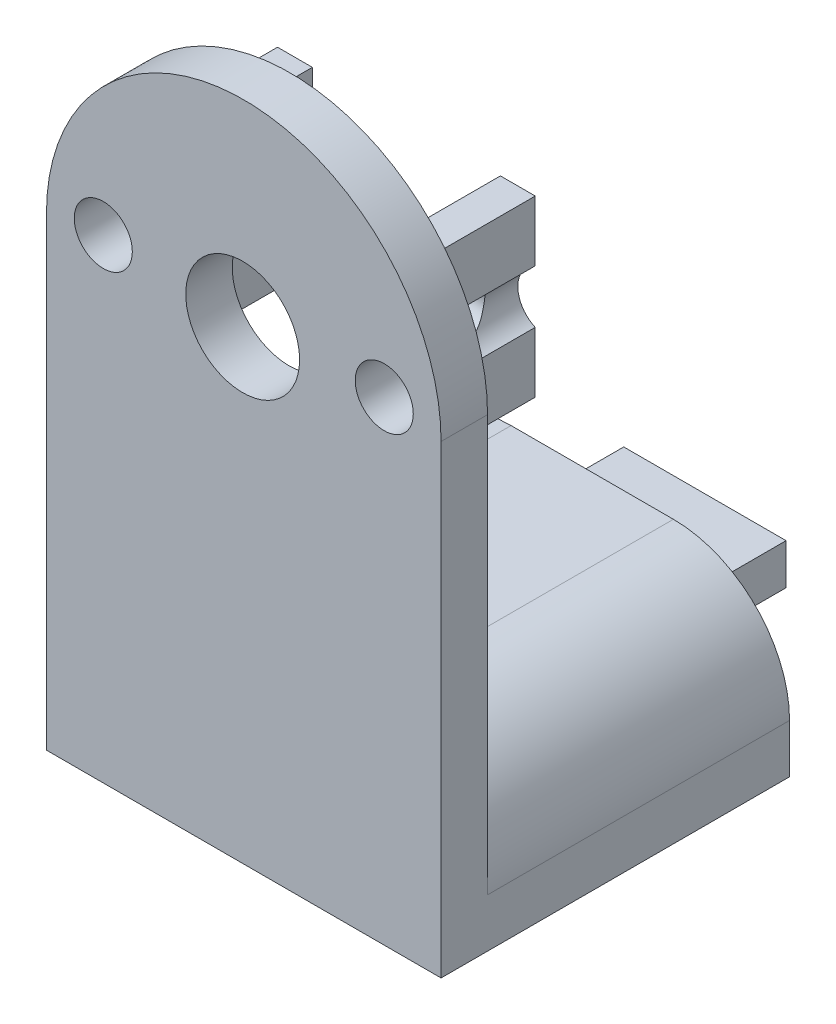
SolidWorks part; units mm, degrees
ref_plane "Front Plane" through (0, 0, 0) normal (0, 0, 1) x (1, 0, 0)
ref_plane "Top Plane" through (0, 0, 0) normal (0, 1, 0) x (1, 0, 0)
ref_plane "Right Plane" through (0, 0, 0) normal (1, 0, 0) x (0, 0, -1)
sketch "Sketch1" plane through (0, 0, 0) normal (0, 1, 0) x (1, 0, 0)
  line L0 (8.6863, 72.103) -> (8.6863, 7.103) construction
  line L1 (8.6863, 7.103) -> (-25.2879, 7.103)
  line L2 (8.6863, 7.103) -> (8.6863, -22.897)
  line L3 (8.6863, -22.897) -> (-25.2879, -22.897)
  line L4 (-25.2879, 7.103) -> (-25.2879, -22.897)
  line L5 (-25.2879, 72.103) -> (-25.2879, 7.103) construction
  point P0 (0, 0)
  dimension "D1" = 30
extrude "Boss-Extrude1" add sketch "Sketch1" along normal blind 11 and the other way blind 3.2
sketch "Sketch2" plane through (0, 0, -7.103) normal (0, 0, -1) x (-1, 0, 0)
  line L0 (-8.6863, -3.2) -> (25.2879, -3.2) construction
  line L1 (1.3137, 4.5571) -> (15.2879, 4.5571)
  line L2 (1.3137, 4.5571) -> (1.3137, 1.044)
  line L3 (1.3137, 1.044) -> (15.2879, 1.044)
  line L4 (15.2879, 4.5571) -> (15.2879, 1.044)
  line L5 (-8.6863, 11) -> (-8.6863, -3.2) construction
  line L6 (25.2879, 11) -> (25.2879, -3.2) construction
  line L7 (8.3008, 4.5571) -> (8.3008, 11)
  line L8 (-8.6863, 11) -> (25.2879, 11) construction
  point P0 (8.3008, 8)
  point P7 (8.3008, -3.2)
  dimension "D1" = 10
  dimension "D2" = 10
extrude "Boss-Extrude2" add sketch "Sketch2" along normal blind 9.7 contours L4 L1 L2 L3 region at (-8.3008, 2.8005, -7.103)
sketch "Sketch13" plane through (0, 0, 22.897) normal (0, 0, 1) x (1, 0, 0)
  line L1 (-25.2879, 11) -> (8.6863, 11)
  line L2 (-25.2879, 11) -> (-25.2879, 36.8)
  line L4 (8.6863, 11) -> (8.6863, 36.8)
  arc A0 (-25.2879, 36.8) -> (8.6863, 36.8) centre (-8.3008, 36.8) cw
  circle A2 centre (-8.3945, 36.8) radius 4.9
extrude "Boss-Extrude6" add sketch "Sketch13" against normal blind 4
sketch "Sketch14" plane through (0, 0, 18.897) normal (0, 0, -1) x (-1, 0, 0)
  line L1 (16.3945, 45.1553) -> (19.3945, 45.1553)
  line L2 (16.3945, 45.1553) -> (16.3945, 30.1553)
  line L3 (16.3945, 30.1553) -> (19.3945, 30.1553)
  line L4 (19.3945, 45.1553) -> (19.3945, 30.1553)
  line L5 (4.1722, 37.6553) -> (36.6168, 37.6553) construction
  circle A0 centre (8.3945, 36.8) radius 4.9 construction
  circle A1 centre (20.3945, 37.6553) radius 2.5
  point P8 (16.3945, 37.6553)
  dimension "D4" = 5
  dimension "D5" = 1
  dimension "D1" = 15
  dimension "D2" = 3
  dimension "D3" = 8
extrude "Boss-Extrude7" add sketch "Sketch14" along normal blind 10 contours L2 L5 A1 L4 L1 | L5 L2 L3 L4 A1 region at (-17.7855, 41.7568, 18.897) region at (-17.7855, 33.5537, 18.897)
extrude "Cut-Extrude4" cut sketch "Sketch14<5>" against normal up to next contours A1 L5 L4 | L5 A1 L4 | L5 L4 A1 | L4 L5 A1 region at (-20.9408, 38.7679, 18.897) region at (-18.7758, 38.5636, 18.897) region at (-18.7758, 36.747, 18.897) region at (-20.9408, 36.5427, 18.897)
sketch "Sketch14<5>" plane through (0, 0, 18.897) normal (0, 0, -1) x (-1, 0, 0) same geometry as "Sketch14"
ref_plane "Plane2" through (-8.3008, 0, 0) normal (-1, 0, 0) x (0, 0, 1)
mirror "Mirror1" about plane through (-8.3008, 0, 0) normal (-1, 0, 0) of "Cut-Extrude4", "Boss-Extrude7"
sketch "Sketch15" plane through (-16.3945, 0, 0) normal (1, 0, 0) x (0, 0, -1)
  circle A0 centre (-13.5581, 38.0239) radius 1.75
  dimension "D1" = 3.5
extrude "Cut-Extrude5" cut sketch "Sketch15" against normal through all both and the other way through all
fillet "Fillet3" radius 10 2 edges at (-25.2879, 11, 5.897) (8.6863, 11, 5.897)
